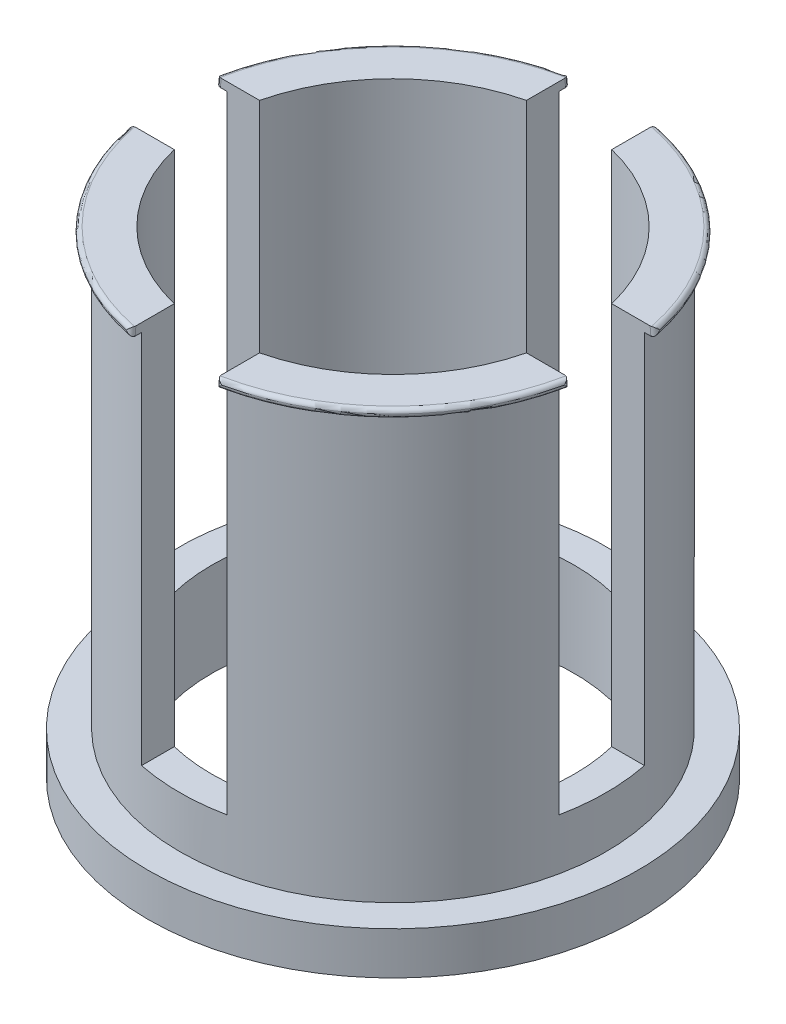
SolidWorks part; units mm, degrees
ref_plane "Front Plane" through (0, 0, 0) normal (0, 0, 1) x (1, 0, 0)
ref_plane "Top Plane" through (0, 0, 0) normal (0, 1, 0) x (1, 0, 0)
ref_plane "Right Plane" through (0, 0, 0) normal (1, 0, 0) x (0, 0, -1)
sketch "Sketch1" plane through (0, 0, 0) normal (0, 1, 0) x (1, 0, 0)
  circle A0 centre (0, 0) radius 12.7
  dimension "D1" = 25.4
extrude "Boss-Extrude1" add sketch "Sketch1" along normal blind 25.4
sketch "Sketch2" plane through (0, 25.4, 0) normal (0, 1, 0) x (1, 0, 0)
  circle A0 centre (0, 0) radius 13.335
  dimension "D1" = 26.67
extrude "Boss-Extrude2" add sketch "Sketch2" along normal blind 0.508
draft "Draft1" type of draft neutral plane draft angle 5 faces to draft 1 face at (0, 25.908, 13.335) neutral plane through (0, 25.908, 0) neutral plane normal (0, 1, 0) parameters "D1"=5
sketch "Sketch5" plane through (0, 0, 0) normal (0, -1, 0) x (1, 0, 0)
  circle A0 centre (0, 0) radius 14.605
  dimension "D1" = 29.21
extrude "Boss-Extrude3" add sketch "Sketch5" along normal blind 2.54 contours A0
sketch "Sketch3" plane through (0, 25.908, 0) normal (0, 1, 0) x (1, 0, 0)
  circle A0 centre (0, 0) radius 10.795
  dimension "D1" = 21.59
extrude "Cut-Extrude1" cut sketch "Sketch3" against normal through all and the other way through all
sketch "Sketch4" plane through (0, 25.908, 0) normal (0, 1, 0) x (1, 0, 0)
  line L0 (0, 13.3794) -> (0, -13.3794) construction
  line L1 (-13.3794, 0) -> (13.3794, 0) construction
  line L3 (-15.24, 2.54) -> (15.24, 2.54)
  line L4 (-15.24, 2.54) -> (-15.24, -2.54)
  line L5 (-15.24, -2.54) -> (15.24, -2.54)
  line L6 (15.24, 2.54) -> (15.24, -2.54)
  line L7 (-15.24, 2.54) -> (15.24, -2.54) construction
  line L8 (-15.24, -2.54) -> (15.24, 2.54) construction
  line L9 (-2.54, -15.24) -> (2.54, -15.24)
  line L10 (-2.54, -15.24) -> (-2.54, 15.24)
  line L11 (-2.54, 15.24) -> (2.54, 15.24)
  line L12 (2.54, -15.24) -> (2.54, 15.24)
  line L13 (-2.54, -15.24) -> (2.54, 15.24) construction
  line L14 (-2.54, 15.24) -> (2.54, -15.24) construction
  circle A0 centre (0, 0) radius 13.3794 construction
  point P7 (0, 0)
  point P13 (0, 0)
  dimension "D1" = 30.48
  dimension "D2" = 5.08
  dimension "D3" = 5.08
  dimension "D4" = 30.48
extrude "Cut-Extrude2" cut sketch "Sketch4" against normal blind 22.86
fillet "Fillet3" radius 0.254 16 edges at (-9.4607, 25.4, 9.4607) (-9.4293, 25.908, 9.4293) (-9.4607, 25.4, -9.4607) (-9.4293, 25.908, -9.4293) (9.4293, 25.908, -9.4293) (9.4607, 25.4, -9.4607) (9.4607, 25.4, 9.4607) (9.4293, 25.908, 9.4293)
